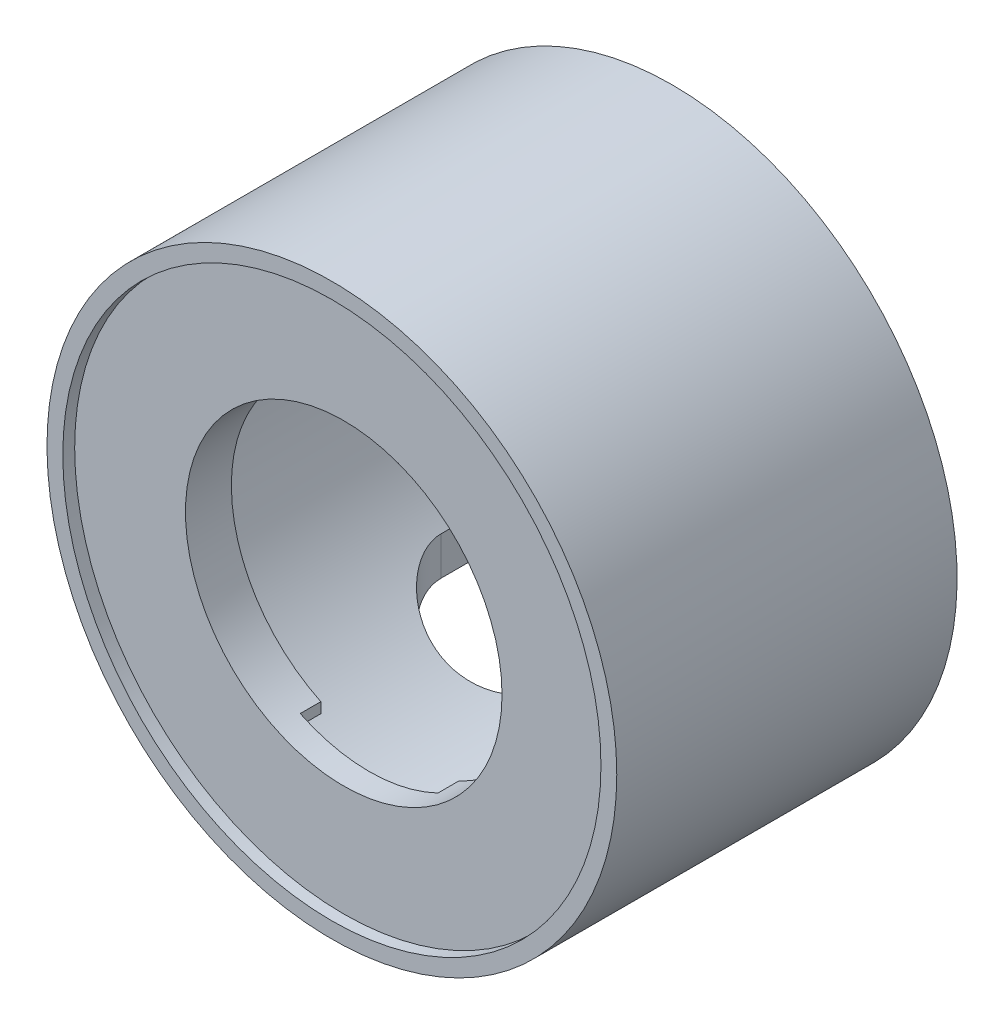
SolidWorks part; units mm, degrees
ref_plane "前视基准面" through (0, 0, 0) normal (0, 0, 1) x (1, 0, 0)
ref_plane "上视基准面" through (0, 0, 0) normal (0, 1, 0) x (1, 0, 0)
ref_plane "右视基准面" through (0, 0, 0) normal (1, 0, 0) x (0, 0, -1)
sketch "草图1" plane through (0, 0, 0) normal (0, 0, 1) x (1, 0, 0)
  circle A0 centre (0, 0) radius 36
  dimension "D1" = 72
extrude "凸台-拉伸1" add sketch "草图1" along normal blind 43
sketch "草图2" plane through (0, 0, 43) normal (0, 0, 1) x (1, 0, 0)
  circle A0 centre (0, 0) radius 34
  dimension "D1" = 68
extrude "切除-拉伸1" cut sketch "草图2" against normal blind 1.5
sketch "草图3" plane through (0, 0, 0) normal (0, 1, 0) x (1, 0, 0)
  line L0 (0, 0) -> (0, -43) construction
  line L1 (36, 0) -> (-36, 0) construction
  line L2 (-36, -43) -> (36, -43) construction
  line L3 (-16.2, -5.5) -> (16.2, -5.5) construction
  line L4 (-23.7, -5.5) -> (-23.7, 0)
  line L5 (-23.7, 0) -> (-8.7, 0)
  line L6 (-8.7, 0) -> (-8.7, -5.5)
  line L7 (8.7, -5.5) -> (8.7, 0)
  line L8 (8.7, 0) -> (23.7, 0)
  line L9 (23.7, 0) -> (23.7, -5.5)
  circle A0 centre (-16.2, -5.5) radius 7.5
  circle A1 centre (16.2, -5.5) radius 7.5
  point P13 (0, -5.5)
  dimension "D1" = 15
  dimension "D2" = 15
  dimension "D3" = 32.4
  dimension "D4" = 5.5
sketch "草图5" plane through (0, 0, 0) normal (0, 0, -1) x (-1, 0, 0)
  circle A0 centre (0, 0) radius 32.5
  dimension "D1" = 65
extrude "切除-拉伸2" cut sketch "草图5" against normal blind 38.3 contours A0
sketch "草图6" plane through (0, 0, 38.3) normal (0, 0, -1) x (-1, 0, 0)
  line L0 (16.2, 0) -> (-16.2, 0) construction
  circle A0 centre (0, 0) radius 20
  circle A1 centre (0, 0) radius 21.2
  dimension "D1" = 40
  dimension "D2" = 42.4
extrude "凸台-拉伸2" add sketch "草图6" along normal blind 2.6 contours A1
extrude "切除-拉伸3" cut sketch "草图6<3>" against normal blind 8.6 and the other way blind 7 contours A0
sketch "草图6<3>" plane through (0, 0, 38.3) normal (0, 0, -1) x (-1, 0, 0) same geometry as "草图6"
extrude "切除-拉伸4" cut sketch "草图3" against normal through all contours A1 L8 | A1 L9 L8 | A1 L8 L7 | A0 L5 L4 | A0 L5 | A0 L6 L5 region at (-16.2, 0, 6.0432) region at (-23.0049, 0, 1.3271) region at (-9.3951, 0, 1.3271) region at (16.2, 0, 6.0432) region at (9.3951, 0, 1.3271) region at (23.0049, 0, 1.3271)
sketch "草图7" plane through (0, 0, 38.3) normal (0, 0, -1) x (-1, 0, 0)
  line L0 (0, 0) -> (0, -32.5) construction
  line L1 (-8.7, -18.0086) -> (-8.7, -19.3326)
  line L2 (8.7, -18.0086) -> (8.7, -19.3326)
  line L3 (-8.7, -34.9329) -> (-8.7, -31.3139) construction
  line L4 (8.7, -34.9329) -> (8.7, -31.3139) construction
  circle A0 centre (0, 0) radius 32.5 construction
  circle A1 centre (0, 0) radius 20 construction
  circle A2 centre (0, 0) radius 21.2 construction
  circle A3 centre (0, 0) radius 21.2 construction
  arc A4 (-8.7, -18.0086) -> (8.7, -18.0086) centre (0, 0) ccw
  arc A5 (-8.7, -19.3326) -> (8.7, -19.3326) centre (0, 0) ccw
extrude "切除-拉伸5" cut sketch "草图7" along normal blind 3
